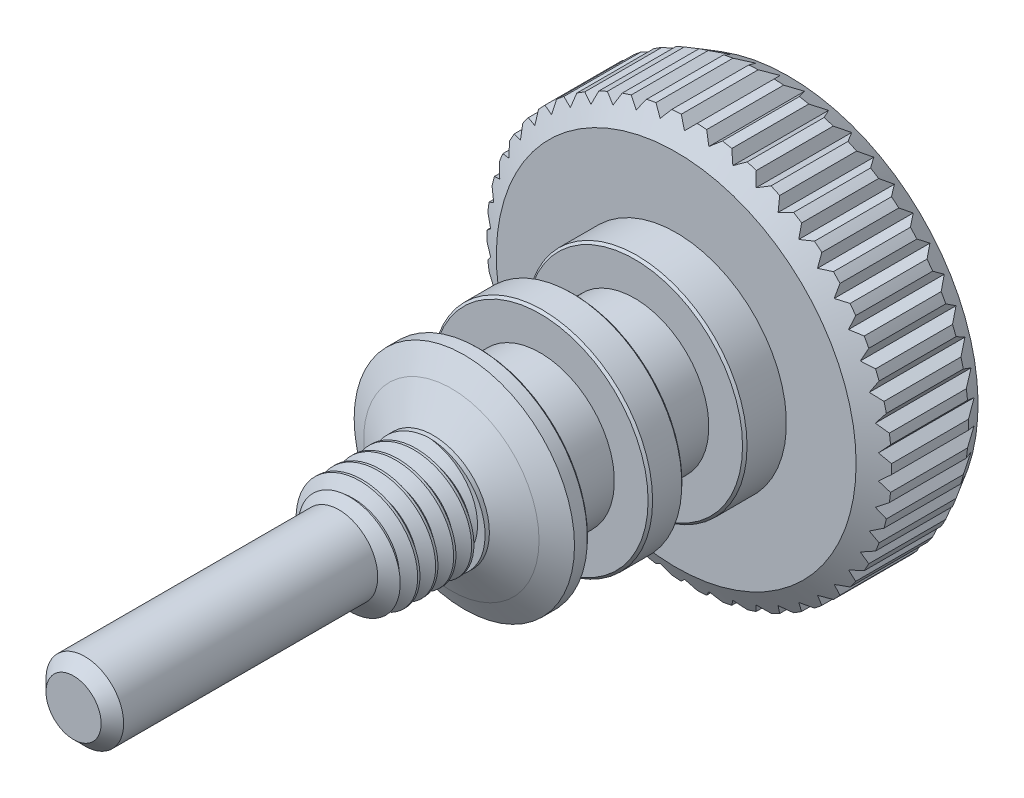
SolidWorks part; units mm, degrees
material "6061-T6 (SS)"
ref_plane "Front Plane" through (0, 0, 0) normal (0, 0, 1) x (1, 0, 0)
ref_plane "Top Plane" through (0, 0, 0) normal (0, 1, 0) x (1, 0, 0)
ref_plane "Right Plane" through (0, 0, 0) normal (1, 0, 0) x (0, 0, -1)
sketch "Sketch1" plane through (0, 0, 0) normal (1, 0, 0) x (0, 0, -1)
  line L0 (0, 0) -> (0, 4.9)
  line L1 (0, 4.9) -> (1.25, 4.9)
  line L2 (1.25, 4.9) -> (1.25, 3.3)
  line L3 (1.25, 3.3) -> (3.95, 3.3)
  line L4 (3.95, 3.3) -> (3.95, 4.9)
  line L5 (3.95, 4.9) -> (5.45, 4.9)
  line L6 (5.45, 4.9) -> (5.45, 3.3)
  line L7 (5.45, 3.3) -> (8.15, 3.3)
  line L8 (8.15, 3.3) -> (8.15, 4.9)
  line L9 (8.15, 4.9) -> (10, 4.9)
  line L11 (15, 0) -> (0, 0)
  line L12 (0, 4.9) -> (0, 5) construction
  line L13 (0, 5) -> (8.15, 5) construction
  line L14 (8.15, 5) -> (8.15, 4.9) construction
  line L15 (10, 4.9) -> (10, 9)
  line L17 (10, 9) -> (15, 9)
  line L18 (15, 9) -> (15, 0)
  circle A0 centre (2.25, 4.3) radius 1 construction
  circle A1 centre (6.45, 4.3) radius 1 construction
  dimension "D6" = 2
  dimension "D1" = 4.9
  dimension "D2" = 2.7
  dimension "D3" = 10
  dimension "D4" = 1.25
  dimension "D5" = 1.5
  dimension "D7" = 5
  dimension "D8" = 1.7
  dimension "D9" = 5
  dimension "D11" = 9
revolve "Revolve1" add sketch "Sketch1" angle 360 about L11
chamfer "Chamfer1" distance 1 angle 30 3 edges at (-9, 0, -10) (-4.9, 0, 0) (-9, 0, -15) first distance on face at (-4.9, 0, -10) first distance on face at (-4.9, 0, 0) first distance on face at (-9, 0, -10)
chamfer "Chamfer2" distance 0.1 angle 45 4 edges at (-4.9, 0, -8.15) (-4.9, 0, -5.45) (-4.9, 0, -3.95) (-4.9, 0, -1.25)
sketch "Sketch2" plane through (0, 0, -15) normal (0, 0, -1) x (-1, 0, 0)
  line L0 (0, 8.6395) -> (-0.3536, 8.9931)
  line L1 (-0.3536, 8.9931) -> (0, 9.3466)
  line L2 (0, 9.3466) -> (0.3536, 8.9931)
  line L3 (0.3536, 8.9931) -> (0, 8.6395)
  circle A0 centre (0, 0) radius 9 construction
  dimension "D1" = 0.5
extrude "Cut-Extrude1" cut sketch "Sketch2" against normal through all
pattern_circular "CirPattern1" count 50 over 360 about axis through (0, 0, -15) along (0, 0, -1) of "Cut-Extrude1"
sketch "Sketch3" plane through (0, 0, 0) normal (0, 0, 1) x (1, 0, 0)
  circle A0 centre (0, 0) radius 2.5
  dimension "D1" = 5
extrude "Boss-Extrude1" add sketch "Sketch3" along normal blind 5
sketch "Sketch4" plane through (0, 0, 0) normal (1, 0, 0) x (0, 0, -1)
  line L0 (-5, 2.5) -> (-5.3, 1.9804)
  line L1 (-5.3, 1.9804) -> (-5.4, 1.9804)
  line L2 (-5.4, 1.9804) -> (-5.7, 2.5)
  line L3 (-5.7, 2.5) -> (-5, 2.5)
  line L4 (-5.55, 2.2402) -> (-5.15, 2.2402) construction
  dimension "D1" = 60
  dimension "D2" = 0.1
  dimension "D3" = 0.4
sketch "Sketch5" plane through (0, 0, 5) normal (0, 0, 1) x (1, 0, 0)
  circle A0 centre (0, 0) radius 2.5 construction
  circle A1 centre (0, 0) radius 2.5
curve "Helix/Spiral1" pitch 0.8 height 4.7 radius 2.5 centre (0, 0, 5) axis (0, 0, -1) start towards (0, 1, 0)
sweep "Cut-Sweep1" cut profiles "Sketch4" path "Helix/Spiral1"
sketch "Sketch6" plane through (0, 0, 0) normal (1, 0, 0) x (0, 0, -1)
  line L0 (-5, 1.7264) -> (-4.4583, 2.5)
  line L1 (-5, 2.5) -> (-5, -1.4003) construction
  line L2 (-4.4583, 2.5) -> (-5, 2.5)
  line L3 (-5, 2.5) -> (-5, 1.7264)
  line L4 (-5.3, 1.9804) -> (-5.4, 1.9804) construction
  line L5 (0, 0) -> (-5, 0) construction
  dimension "D1" = 55
  dimension "D2" = 0.254
revolve "Cut-Revolve1" cut sketch "Sketch6" angle 360 about L5
sketch "Sketch7" plane through (0, 0, 0) normal (0, 0, 1) x (1, 0, 0)
  circle A0 centre (0, 0) radius 2.5 construction
  circle A1 centre (0, 0) radius 2.5
extrude "Boss-Extrude2" add sketch "Sketch7" along normal blind 1
sketch "Sketch8" plane through (0, 0, 5) normal (0, 0, 1) x (1, 0, 0)
  circle A0 centre (0, 0) radius 1.7264
extrude "Boss-Extrude3" add sketch "Sketch8" along normal blind 11.8
chamfer "Chamfer3" distance 0.5 angle 45 1 edges at (1.7264, 0, 16.8)
chamfer "Chamfer4" distance 1.4 angle 30 1 edges at (2.5, 0, 0) first distance on face at (3.9, 0, 0)
